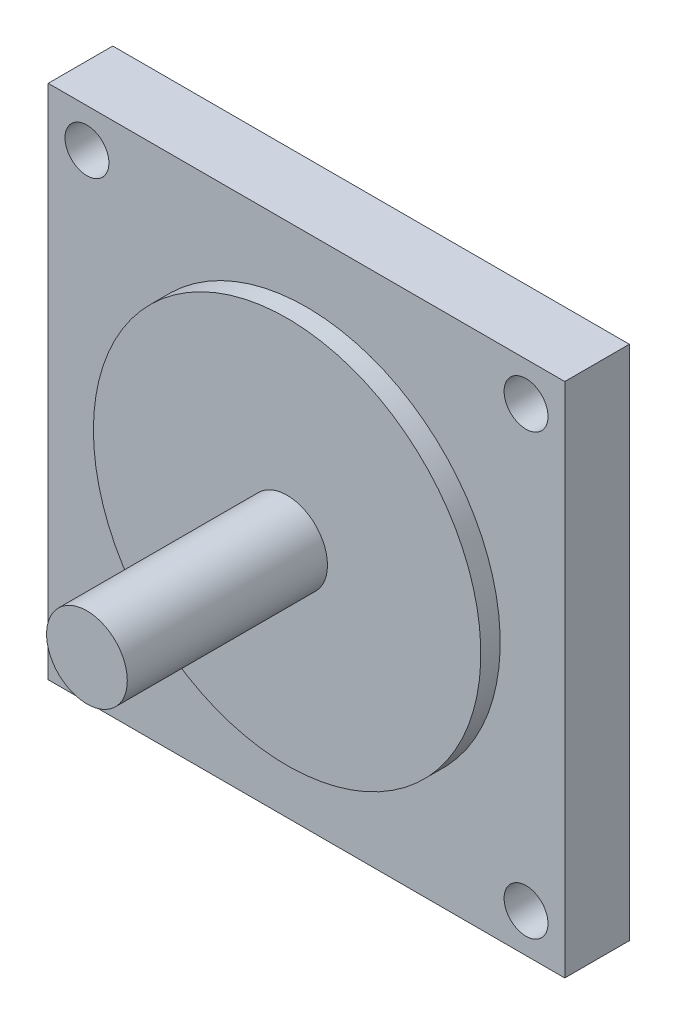
SolidWorks part; units mm, degrees
ref_plane "Front Plane" through (0, 0, 0) normal (0, 0, 1) x (1, 0, 0)
ref_plane "Top Plane" through (0, 0, 0) normal (0, 1, 0) x (1, 0, 0)
ref_plane "Right Plane" through (0, 0, 0) normal (1, 0, 0) x (0, 0, -1)
sketch "Sketch1" plane through (0, 0, 0) normal (0, 0, 1) x (1, 0, 0)
  line L1 (-50.8, 50.8) -> (50.8, 50.8)
  line L2 (-50.8, 50.8) -> (-50.8, -50.8)
  line L3 (-50.8, -50.8) -> (50.8, -50.8)
  line L4 (50.8, 50.8) -> (50.8, -50.8)
  line L5 (-50.8, 50.8) -> (50.8, -50.8) construction
  line L6 (-50.8, -50.8) -> (50.8, 50.8) construction
  circle A0 centre (-43.18, -43.18) radius 4.318
  circle A1 centre (43.18, -43.18) radius 4.318
  circle A2 centre (43.18, 43.18) radius 4.318
  circle A3 centre (-43.18, 43.18) radius 4.318
  point P0 (0, 0)
  point P14 (0, 0)
  point P15 (0, 0)
  dimension "D4" = 8.636
  dimension "D5" = 8.636
  dimension "D6" = 8.636
  dimension "D7" = 8.636
  dimension "D1" = 101.6
  dimension "D2" = 101.6
  dimension "D3" = 86.36
extrude "Boss-Extrude1" add sketch "Sketch1" along normal blind 12.7
sketch "Sketch2" plane through (0, 0, 12.7) normal (0, 0, 1) x (1, 0, 0)
  circle A0 centre (0, 0) radius 38.1
  dimension "D1" = 76.2
extrude "Boss-Extrude2" add sketch "Sketch2" along normal blind 3.81
sketch "Sketch4" plane through (0, 0, 16.51) normal (0, 0, 1) x (1, 0, 0)
  circle A0 centre (0, 0) radius 7.9375
  dimension "D1" = 15.875
extrude "Boss-Extrude4" add sketch "Sketch4" along normal blind 39.37
sketch "Sketch5" plane through (0, 0, 12.7) normal (0, 0, 1) x (1, 0, 0)
  line L0 (2.7107, 7.4603) -> (2.7107, 6.51)
  line L2 (-2.3876, 7.5699) -> (-2.3876, 7.929)
  circle A3 centre (0, 0) radius 7.9375 construction
  dimension "D3" = 0.3591
